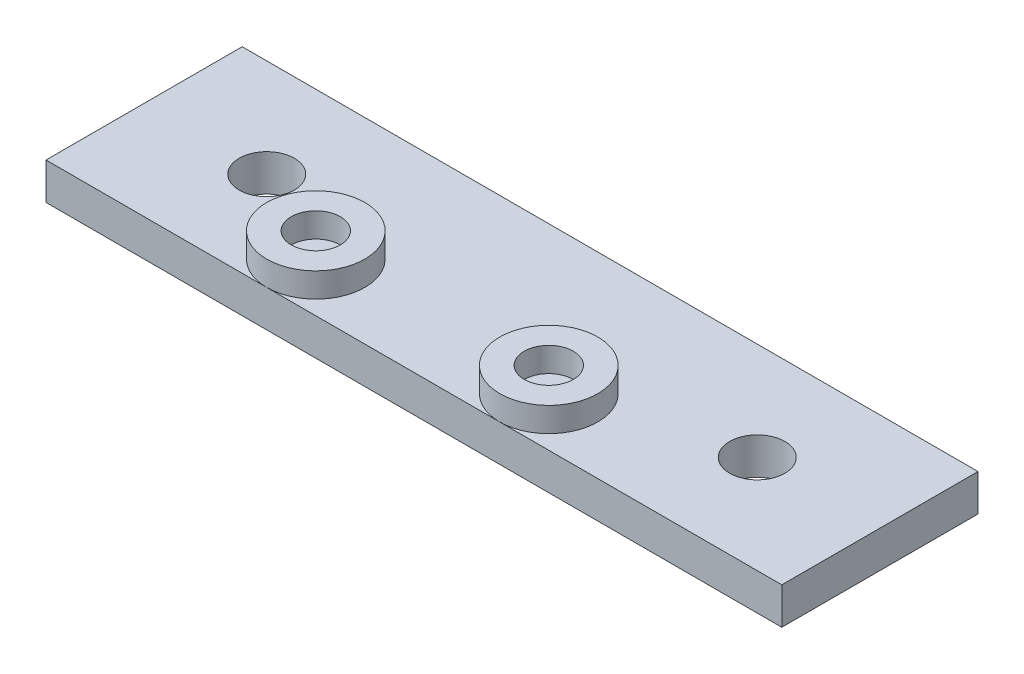
SolidWorks part; units mm, degrees
ref_plane "Front Plane" through (0, 0, 0) normal (0, 0, 1) x (1, 0, 0)
ref_plane "Top Plane" through (0, 0, 0) normal (0, 1, 0) x (1, 0, 0)
ref_plane "Right Plane" through (0, 0, 0) normal (1, 0, 0) x (0, 0, -1)
sketch "Sketch1" plane through (0, 0, 0) normal (0, 1, 0) x (1, 0, 0)
  circle A0 centre (0, 0) radius 2
  circle A1 centre (19, 0) radius 2
  circle A2 centre (0, 0) radius 4
  circle A3 centre (19, 0) radius 4
  dimension "D1" = 19
  dimension "D2" = 4
  dimension "D3" = 4
  dimension "D4" = 8
  dimension "D5" = 8
extrude "Boss-Extrude1" add sketch "Sketch1" along normal blind 2
sketch "Sketch2" plane through (0, 0, 0) normal (0, -1, 0) x (1, 0, 0)
  line L1 (-18, 4) -> (42, 4)
  line L2 (-18, 4) -> (-18, -12)
  line L3 (-18, -12) -> (42, -12)
  line L4 (42, 4) -> (42, -12)
  circle A0 centre (0, 0) radius 4 construction
  circle A1 centre (19, 0) radius 4 construction
  circle A2 centre (-8, -4) radius 2.25
  circle A3 centre (32, -4) radius 2.25
  dimension "D3" = 18
  dimension "D4" = 4
  dimension "D5" = 4
  dimension "D6" = 8
  dimension "D7" = 10
  dimension "D8" = 10
  dimension "D9" = 8
  dimension "D10" = 4.5
  dimension "D11" = 4.5
  dimension "D1" = 16
  dimension "D2" = 60
extrude "Boss-Extrude2" add sketch "Sketch2" along normal blind 3
